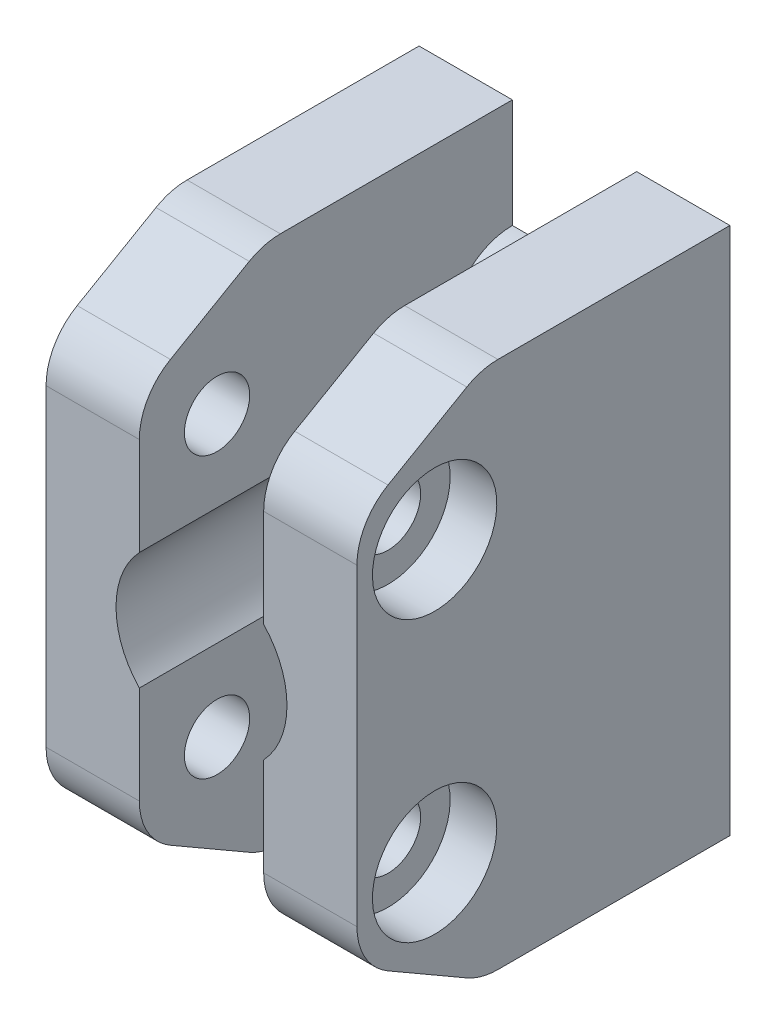
SolidWorks part; units mm, degrees
ref_plane "Plan de face" through (0, 0, 0) normal (0, 0, 1) x (1, 0, 0)
ref_plane "Plan de dessus" through (0, 0, 0) normal (0, 1, 0) x (1, 0, 0)
ref_plane "Plan de droite" through (0, 0, 0) normal (1, 0, 0) x (0, 0, -1)
sketch "Esquisse1" plane through (0, 0, 0) normal (0, 0, 1) x (1, 0, 0)
  line L1 (-10, 17) -> (10, 17)
  line L2 (-10, 17) -> (-10, -17)
  line L3 (-10, -17) -> (10, -17)
  line L4 (10, 17) -> (10, -17)
  dimension "D1" = 34
  dimension "D2" = 10
  dimension "D3" = 20
  dimension "D4" = 17
extrude "Boss.-Extru.1" add sketch "Esquisse1" along normal blind 4
sketch "Esquisse2" plane through (0, 0, 4) normal (0, 0, 1) x (1, 0, 0)
  line L0 (10, 17) -> (-10, 17) construction
  line L1 (-4, 17) -> (4, 17)
  line L2 (-4, 17) -> (-4, 10)
  line L3 (-4, 10) -> (4, 10)
  line L4 (4, 17) -> (4, 10)
  line L5 (10, -17) -> (10, 17) construction
  line L6 (-4, -17) -> (4, -17)
  line L7 (-4, -17) -> (-4, -10)
  line L8 (-4, -10) -> (4, -10)
  line L9 (4, -17) -> (4, -10)
  line L10 (-10, -17) -> (10, -17) construction
  dimension "D1" = 8
  dimension "D2" = 6
  dimension "D3" = 6
  dimension "D4" = 8
  dimension "D5" = 20
extrude "Enlèv. mat.-Extru.1" cut sketch "Esquisse2" against normal through all
fillet "Congé1" radius 4 2 edges at (0, -10, 4) (0, 10, 4)
sketch "Esquisse3" plane through (0, 0, 4) normal (0, 0, 1) x (1, 0, 0)
  line L1 (-10, 17) -> (-4, 17)
  line L2 (-10, 17) -> (-10, -17)
  line L3 (-10, -17) -> (-4, -17)
  line L4 (-4, 17) -> (-4, -17)
  line L5 (4, -17) -> (10, -17)
  line L6 (4, -17) -> (4, 17)
  line L7 (4, 17) -> (10, 17)
  line L8 (10, -17) -> (10, 17)
extrude "Boss.-Extru.2" add sketch "Esquisse3" along normal blind 20
sketch "Esquisse4" plane through (10, 0, 0) normal (1, 0, 0) x (0, 0, -1)
  line L0 (-24, -17) -> (0, -17) construction
  line L3 (-24, -17) -> (-24, 17) construction
  circle A0 centre (-19, 9) radius 2.1
  circle A1 centre (-19, -9) radius 2.1
  dimension "D1" = 4.2
  dimension "D2" = 4.2
  dimension "D3" = 18
  dimension "D4" = 8
  dimension "D5" = 5
  dimension "D6" = 5
extrude "Enlèv. mat.-Extru.2" cut sketch "Esquisse4" against normal through all
chamfer "Chanfrein1" distance 8 angle 30 4 edges at (-7, -17, 24) (7, -17, 24) (-7, 17, 24) (7, 17, 24) first distance on face at (-7, -17, 12) first distance on face at (7, -17, 12) first distance on face at (-7, 17, 12) first distance on face at (7, 17, 12)
fillet "Congé2" radius 4 8 edges at (7, 17, 16) (-7, 17, 16) (-7, 12.3812, 24) (7, 12.3812, 24) (7, -12.3812, 24) (7, -17, 16) (-7, -17, 16) (-7, -12.3812, 24)
sketch "Esquisse5" plane through (0, 0, 4) normal (0, 0, 1) x (1, 0, 0)
  circle A0 centre (0, 0) radius 3.2
  dimension "D1" = 6.4
extrude "Enlèv. mat.-Extru.3" cut sketch "Esquisse5" against normal through all
sketch "Esquisse6" plane through (0, 0, 4) normal (0, 0, 1) x (1, 0, 0)
  circle A0 centre (0, 0) radius 5.5
  dimension "D1" = 11
extrude "Enlèv. mat.-Extru.4" cut sketch "Esquisse6" along normal through all
sketch "Esquisse7" plane through (10, 0, 0) normal (1, 0, 0) x (0, 0, -1)
  circle A0 centre (-19, 9) radius 4
  circle A1 centre (-19, -9) radius 4
  dimension "D1" = 8
  dimension "D2" = 8
extrude "Enlèv. mat.-Extru.5" cut sketch "Esquisse7" against normal blind 3
